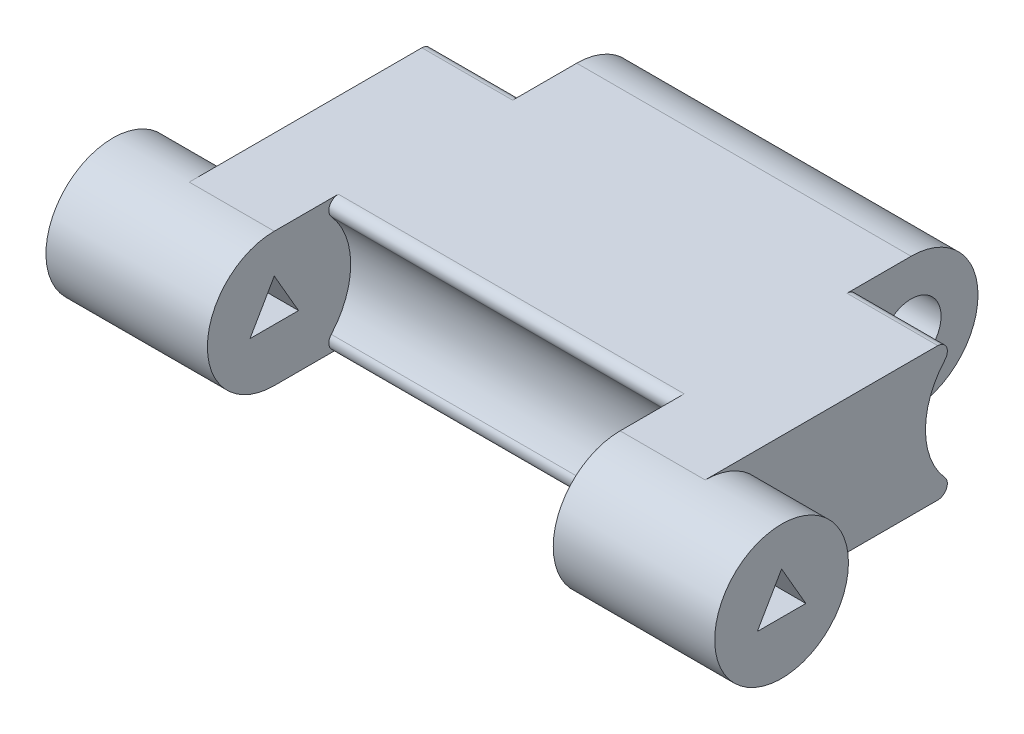
SolidWorks part; units mm, degrees
ref_plane "Спереди" through (0, 0, 0) normal (0, 0, 1) x (1, 0, 0)
ref_plane "Сверху" through (0, 0, 0) normal (0, 1, 0) x (1, 0, 0)
ref_plane "Справа" through (0, 0, 0) normal (1, 0, 0) x (0, 0, -1)
sketch "Эскиз1" plane through (0, 0, 0) normal (1, 0, 0) x (0, 0, -1)
  line L0 (-7.765, 3.5) -> (7.765, 3.5) construction
  line L1 (-7.765, 7) -> (7.765, 7)
  line L2 (-7.765, 0) -> (7.765, 0)
  arc A0 (-7.765, 7) -> (-7.765, 0) centre (-7.765, 3.5) ccw
  arc A1 (7.765, 0) -> (7.765, 7) centre (7.765, 3.5) ccw
  point P2 (0, 3.5)
  dimension "D1" = 15.53
  dimension "D2" = 7
extrude "Бобышка-Вытянуть1" add sketch "Эскиз1" along normal mid plane 35
sketch "Эскиз3" plane through (17.5, 0, 0) normal (1, 0, 0) x (0, 0, -1)
  line L0 (7.765, 7) -> (-7.765, 7) construction
  line L1 (-12, 8) -> (12, 8)
  line L2 (-12, 8) -> (-12, -1)
  line L3 (-12, -1) -> (12, -1)
  line L4 (12, 8) -> (12, -1)
  line L5 (-12, 8) -> (12, -1) construction
  line L6 (-12, -1) -> (12, 8) construction
  line L7 (-7.765, 0) -> (7.765, 0) construction
  circle A0 centre (-7.765, 3.5) radius 3.5
  arc A1 (-7.765, 7) -> (-7.765, 0) centre (-7.765, 3.5) ccw construction
  point P9 (0, 3.5)
  dimension "D1" = 1
  dimension "D2" = 1
  dimension "D3" = 12
  dimension "D4" = 24
extrude "Вырез-Вытянуть1" cut sketch "Эскиз3" against normal blind 4
mirror "Зеркальное отражение1" about plane through (0, 0, 0) normal (1, 0, 0) of "Вырез-Вытянуть1"
sketch "Эскиз6" plane through (0, 0, 0) normal (1, 0, 0) x (0, 0, -1)
  circle A0 centre (-7.765, 3.5) radius 4
  circle A1 centre (-7.765, 3.5) radius 3.5 construction
  dimension "D1" = 8
extrude "Вырез-Вытянуть2" cut sketch "Эскиз6" against normal mid plane 18.1
sketch "Эскиз7" plane through (13.5, 0, 0) normal (1, 0, 0) x (0, 0, -1)
  circle A0 centre (7.765, 3.5) radius 4
  arc A1 (7.765, 0) -> (7.765, 7) centre (7.765, 3.5) ccw construction
  dimension "D2" = 8
  dimension "D1" = 0
extrude "Вырез-Вытянуть3" cut sketch "Эскиз7" against normal blind 4.75
mirror "Зеркальное отражение2" about plane through (0, 0, 0) normal (1, 0, 0) of "Вырез-Вытянуть3"
sketch "Эскиз8" plane through (17.5, 0, 0) normal (1, 0, 0) x (0, 0, -1)
  line L0 (-9.0352, 2.7667) -> (-7.765, 4.9667)
  line L1 (-7.765, 4.9667) -> (-6.4948, 2.7667)
  line L2 (-6.4948, 2.7667) -> (-9.0352, 2.7667)
  circle A1 centre (7.765, 3.5) radius 1.5667
  arc A2 (7.765, 0) -> (7.765, 7) centre (7.765, 3.5) ccw construction
  circle A4 centre (-7.765, 3.5) radius 1.4667 construction
  circle A5 centre (7.765, 3.5) radius 1.4667 construction
  dimension "D1" = 0.1
  dimension "D2" = 2.2
extrude "Вырез-Вытянуть4" cut sketch "Эскиз8" against normal through all
fillet "Скругление1" radius 0.5 6 edges at (-11.125, 0, -5.8285) (-11.125, 7, -5.8285) (0, 7, 5.8285) (0, 0, 5.8285) (11.125, 7, -5.8285) (11.125, 0, -5.8285)
ref_plane "Плоскость4" through (-13.5, 0, 0) normal (-1, 0, 0) x (0, 0, 1)
sketch "Эскиз9" plane through (-17.5, 0, 0) normal (-1, 0, 0) x (0, 0, 1)
  circle A0 centre (7.765, 3.5) radius 0.75
  circle A1 centre (7.765, 3.5) radius 3.5
  circle A2 centre (7.765, 3.5) radius 3.5
  dimension "D2" = 1.5
  dimension "D1" = 0
extrude "Бобышка-Вытянуть2" add sketch "Эскиз9" against normal blind 1
